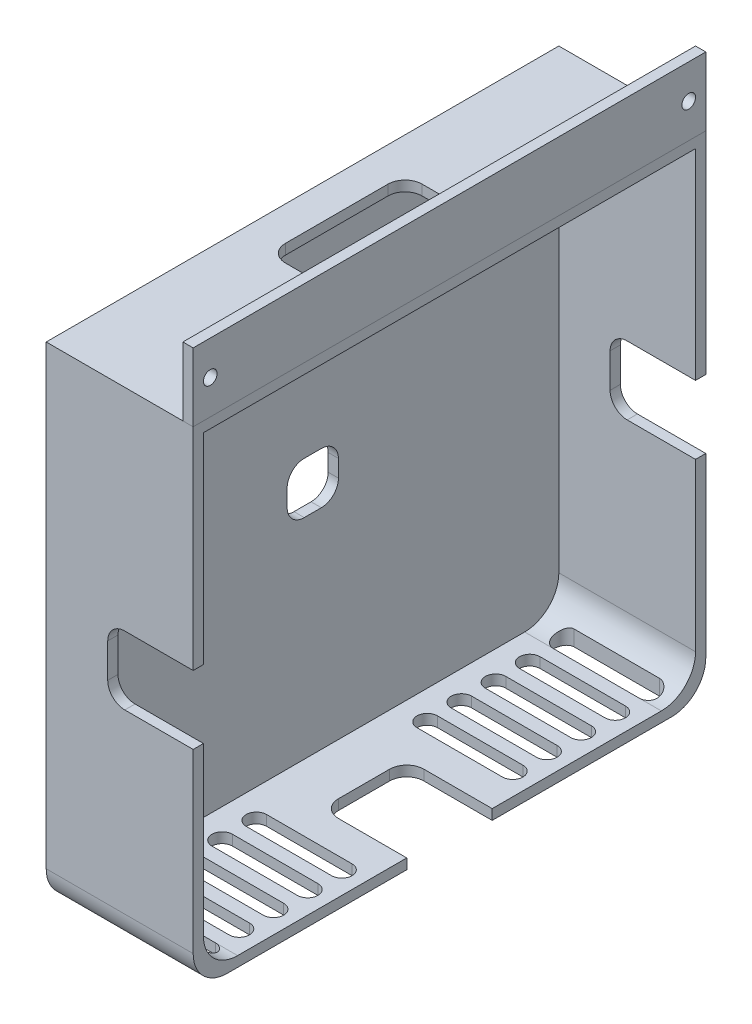
SolidWorks part; units mm, degrees
ref_plane "前视基准面" through (0, 0, 0) normal (0, 0, 1) x (1, 0, 0)
ref_plane "上视基准面" through (0, 0, 0) normal (0, 1, 0) x (1, 0, 0)
ref_plane "右视基准面" through (0, 0, 0) normal (1, 0, 0) x (0, 0, -1)
other "Configuration Table"
sketch "草图1" plane through (0, 0, 0) normal (1, 0, 0) x (0, 0, -1)
  line L1 (-75, 71.75) -> (75, 71.75)
  line L2 (-75, 71.75) -> (-75, -71.75)
  line L3 (-75, -71.75) -> (75, -71.75)
  line L4 (75, 71.75) -> (75, -71.75)
  dimension "D1" = 143.5
  dimension "D2" = 150
  dimension "D3" = 75
  dimension "D4" = 71.75
extrude "凸台-拉伸1" add sketch "草图1" along normal blind 3
sketch "草图2" plane through (3, 0, 0) normal (1, 0, 0) x (0, 0, -1)
  line L0 (72, 68.75) -> (-72, 68.75)
  line L1 (-72, 68.75) -> (-72, -68.75)
  line L2 (-72, -68.75) -> (72, -68.75)
  line L3 (72, -68.75) -> (72, 68.75)
  line L4 (-75, 71.75) -> (-75, -71.75)
  line L5 (-75, -71.75) -> (75, -71.75)
  line L6 (75, -71.75) -> (75, 71.75)
  line L12 (75, 71.75) -> (-75, 71.75)
  line L13 (-75, 71.75) -> (-75, -71.75)
  line L14 (-75, -71.75) -> (75, -71.75)
  line L15 (75, -71.75) -> (75, 71.75)
  line L16 (75, 71.75) -> (-75, 71.75)
  dimension "D1" = 0
  dimension "D2" = 3
extrude "凸台-拉伸2" add sketch "草图2" along normal blind 40
sketch "草图3" plane through (43, 0, 0) normal (1, 0, 0) x (0, 0, -1)
  line L0 (75, -71.75) -> (75, 71.75) construction
  line L1 (-75, 71.75) -> (75, 71.75)
  line L2 (-75, 71.75) -> (-75, 91.75)
  line L3 (-75, 91.75) -> (75, 91.75)
  line L4 (75, 71.75) -> (75, 91.75)
  dimension "D1" = 20
extrude "凸台-拉伸3" add sketch "草图3" against normal blind 3 separate body
sketch "草图4" plane through (40, 0, 0) normal (-1, 0, 0) x (0, 0, 1)
  line L0 (-75, 91.75) -> (75, 91.75) construction
  line L1 (-75, 71.75) -> (-75, 91.75) construction
  circle A0 centre (-70, 81.75) radius 2
  circle A1 centre (70, 81.75) radius 2
  dimension "D1" = 140
  dimension "D4" = 4
  dimension "D2" = 10
  dimension "D3" = 5
extrude "切除-拉伸1" cut sketch "草图4" against normal blind 3
sketch "草图5" plane through (0, 0, -75) normal (0, 0, -1) x (-1, 0, 0)
  line L0 (-43, -71.75) -> (-43, 71.75) construction
  line L1 (-43, 10) -> (-18, 10)
  line L2 (-43, 10) -> (-43, -10)
  line L3 (-43, -10) -> (-18, -10)
  line L4 (-18, 10) -> (-18, -10)
  dimension "D1" = 20
  dimension "D2" = 10
  dimension "D3" = 25
extrude "切除-拉伸2" cut sketch "草图5" against normal through all
fillet "圆角1" radius 5 4 edges at (18, -10, 73.5) (18, 10, 73.5) (18, 10, -73.5) (18, -10, -73.5)
sketch "草图6" plane through (0, -71.75, 0) normal (0, -1, 0) x (1, 0, 0)
  line L0 (43, 75) -> (43, -75) construction
  line L1 (43, 12.5) -> (18, 12.5)
  line L2 (43, 12.5) -> (43, -12.5)
  line L3 (43, -12.5) -> (18, -12.5)
  line L4 (18, 12.5) -> (18, -12.5)
  dimension "D1" = 25
  dimension "D2" = 12.5
  dimension "D3" = 25
extrude "切除-拉伸3" cut sketch "草图6" against normal blind 3 and the other way through all
fillet "圆角2" radius 5 2 edges at (18, -70.25, 12.5) (18, -70.25, -12.5)
sketch "草图8" plane through (0, -71.75, 0) normal (0, -1, 0) x (1, 0, 0)
  line L0 (11.5, -65) -> (36.5, -65) construction
  line L1 (11.5, -62) -> (36.5, -62)
  line L2 (11.5, -68) -> (36.5, -68)
  line L3 (0, 75) -> (0, -75) construction
  line L4 (43, -75) -> (0, -75) construction
  line L5 (11.5, -55) -> (36.5, -55) construction
  line L6 (11.5, -52) -> (36.5, -52)
  line L7 (11.5, -58) -> (36.5, -58)
  line L8 (11.5, -45) -> (36.5, -45) construction
  line L9 (11.5, -42) -> (36.5, -42)
  line L10 (11.5, -48) -> (36.5, -48)
  line L11 (11.5, -35) -> (36.5, -35) construction
  line L12 (11.5, -32) -> (36.5, -32)
  line L13 (11.5, -38) -> (36.5, -38)
  line L14 (11.5, -25) -> (36.5, -25) construction
  line L15 (11.5, -22) -> (36.5, -22)
  line L16 (11.5, -28) -> (36.5, -28)
  line L17 (0, 0) -> (50000, 0) construction
  line L18 (11.5, 25) -> (36.5, 25) construction
  line L19 (11.5, 22) -> (36.5, 22)
  line L20 (11.5, 28) -> (36.5, 28)
  line L21 (11.5, 35) -> (36.5, 35) construction
  line L22 (11.5, 32) -> (36.5, 32)
  line L23 (11.5, 38) -> (36.5, 38)
  line L24 (11.5, 45) -> (36.5, 45) construction
  line L25 (11.5, 42) -> (36.5, 42)
  line L26 (11.5, 48) -> (36.5, 48)
  line L27 (11.5, 55) -> (36.5, 55) construction
  line L28 (11.5, 52) -> (36.5, 52)
  line L29 (11.5, 58) -> (36.5, 58)
  line L30 (11.5, 65) -> (36.5, 65) construction
  line L31 (11.5, 62) -> (36.5, 62)
  line L32 (11.5, 68) -> (36.5, 68)
  arc A0 (11.5, -62) -> (11.5, -68) centre (11.5, -65) ccw
  arc A1 (36.5, -68) -> (36.5, -62) centre (36.5, -65) ccw
  arc A2 (11.5, -52) -> (11.5, -58) centre (11.5, -55) ccw
  arc A3 (36.5, -58) -> (36.5, -52) centre (36.5, -55) ccw
  arc A4 (11.5, -42) -> (11.5, -48) centre (11.5, -45) ccw
  arc A5 (36.5, -48) -> (36.5, -42) centre (36.5, -45) ccw
  arc A6 (11.5, -32) -> (11.5, -38) centre (11.5, -35) ccw
  arc A7 (36.5, -38) -> (36.5, -32) centre (36.5, -35) ccw
  arc A8 (11.5, -22) -> (11.5, -28) centre (11.5, -25) ccw
  arc A9 (36.5, -28) -> (36.5, -22) centre (36.5, -25) ccw
  arc A10 (11.5, 22) -> (11.5, 28) centre (11.5, 25) cw
  arc A11 (36.5, 28) -> (36.5, 22) centre (36.5, 25) cw
  arc A12 (11.5, 32) -> (11.5, 38) centre (11.5, 35) cw
  arc A13 (36.5, 38) -> (36.5, 32) centre (36.5, 35) cw
  arc A14 (11.5, 42) -> (11.5, 48) centre (11.5, 45) cw
  arc A15 (36.5, 48) -> (36.5, 42) centre (36.5, 45) cw
  arc A16 (11.5, 52) -> (11.5, 58) centre (11.5, 55) cw
  arc A17 (36.5, 58) -> (36.5, 52) centre (36.5, 55) cw
  arc A18 (11.5, 62) -> (11.5, 68) centre (11.5, 65) cw
  arc A19 (36.5, 68) -> (36.5, 62) centre (36.5, 65) cw
  point P2 (24, -65)
  point P14 (24, -55)
  point P21 (24, -45)
  point P28 (24, -35)
  point P35 (24, -25)
  point P44 (24, 25)
  point P51 (24, 35)
  point P58 (24, 45)
  point P65 (24, 55)
  point P72 (24, 65)
  dimension "D4" = 3
  dimension "D1" = 25
  dimension "D2" = 11.5
  dimension "D3" = 10
  dimension "D5" = 5
extrude "切除-拉伸4" cut sketch "草图8" against normal blind 3
sketch "草图10" plane through (0, 0, 0) normal (-1, 0, 0) x (0, 0, 1)
  line L1 (-7.5, 7.5) -> (7.5, 7.5)
  line L2 (-7.5, 7.5) -> (-7.5, -7.5)
  line L3 (-7.5, -7.5) -> (7.5, -7.5)
  line L4 (7.5, 7.5) -> (7.5, -7.5)
  dimension "D1" = 15
  dimension "D2" = 7.5
  dimension "D3" = 7.5
extrude "切除-拉伸5" cut sketch "草图10" against normal blind 3
fillet "圆角3" radius 5 4 edges at (1.5, -7.5, 7.5) (1.5, -7.5, -7.5) (1.5, 7.5, -7.5) (1.5, 7.5, 7.5)
sketch "草图11" plane through (0, 71.75, 0) normal (0, 1, 0) x (1, 0, 0)
  line L0 (40, 75) -> (40, -75) construction
  line L7 (40, 20) -> (10, 20)
  line L8 (40, 20) -> (40, -20)
  line L9 (40, -20) -> (10, -20)
  line L10 (10, 20) -> (10, -20)
  dimension "D1" = 40
  dimension "D2" = 20
  dimension "D3" = 30
extrude "切除-拉伸6" cut sketch "草图11" against normal blind 3
fillet "圆角4" radius 5 4 edges at (40, 70.25, -20) (40, 70.25, 20) (10, 70.25, 20) (10, 70.25, -20)
fillet "圆角5" radius 10 1 edges at (23, -68.75, -72)
fillet "圆角6" radius 10 1 edges at (23, -68.75, 72)
fillet "圆角7" radius 10 2 edges at (21.5, -71.75, 75) (21.5, -71.75, -75)
